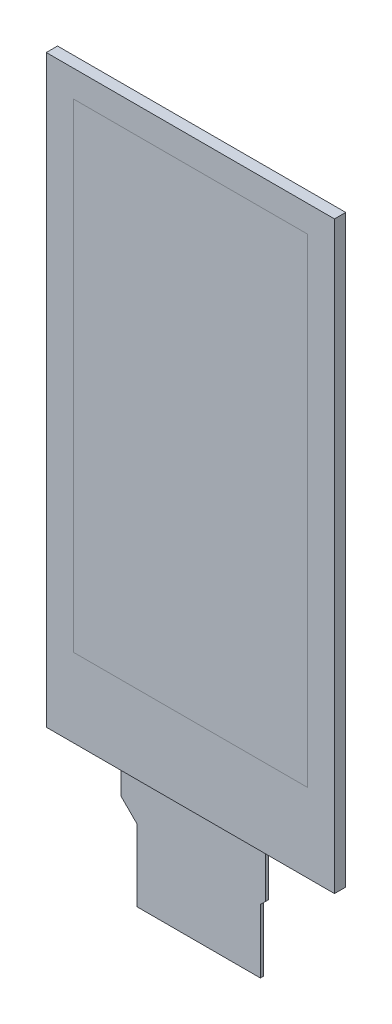
SolidWorks part; units mm, degrees
ref_plane "Front Plane" through (0, 0, 0) normal (0, 0, 1) x (1, 0, 0)
ref_plane "Top Plane" through (0, 0, 0) normal (0, 1, 0) x (1, 0, 0)
ref_plane "Right Plane" through (0, 0, 0) normal (1, 0, 0) x (0, 0, -1)
sketch "Sketch1" plane through (0, 0, 0) normal (0, 0, 1) x (1, 0, 0)
  line L0 (-7.883, -32.225) -> (-7.883, -35.3172)
  line L1 (11.8525, 24.275) -> (-11.8525, 24.275)
  line L2 (11.8525, 24.275) -> (11.8525, -24.275)
  line L3 (11.8525, -24.275) -> (-11.8525, -24.275)
  line L4 (-11.8525, 24.275) -> (-11.8525, -24.275)
  line L5 (0, -24.275) -> (0, 24.275) construction
  line L6 (11.8525, 0) -> (-11.8525, 0) construction
  line L7 (14.6005, 26.975) -> (-14.5995, 26.975)
  line L8 (14.6005, 26.975) -> (14.6005, -32.225)
  line L9 (14.6005, -32.225) -> (-14.5995, -32.225)
  line L10 (-14.5995, 26.975) -> (-14.5995, -32.225)
  line L11 (0.0005, -32.225) -> (0.0005, 26.975) construction
  line L12 (14.6005, -2.625) -> (-14.5995, -2.625) construction
  line L13 (-7.883, -35.3172) -> (-6.2495, -36.9508)
  line L14 (-6.2495, -36.9508) -> (-6.2495, -44.225)
  line L15 (-6.2495, -44.225) -> (6.2505, -44.225)
  line L16 (6.2505, -44.225) -> (6.2505, -37.7718)
  line L17 (6.2505, -37.7718) -> (6.7703, -37.252)
  line L18 (6.7703, -37.252) -> (6.7703, -32.225)
  point P0 (0, 0)
  point P4 (0.0005, -2.625)
  point P10 (0, 0)
  point P17 (15.5111, 26.7095)
  point P18 (6.2505, -35.7718)
  dimension "D1" = 23.705
  dimension "D2" = 29.2
  dimension "D3" = 48.55
  dimension "D4" = 59.2
  dimension "D5" = 12.5
  dimension "D6" = 8.35
  dimension "D7" = 2.748
  dimension "D8" = 2.7
  dimension "D9" = 135
  dimension "D10" = 135
  dimension "D11" = 12
extrude "Boss-Extrude1" add sketch "Sketch1" along normal blind 1.14 contours L1 L4 L3 L2 region at (0, 0, 0)
extrude "Boss-Extrude2" add sketch "Sketch1<3>" along normal blind 1.14 separate body contours L7 L10 L9 L8 L4 L1 L2 L3 region at (-11.2413, -31.5649, 0)
sketch "Sketch1<3>" plane through (0, 0, 0) normal (0, 0, 1) x (1, 0, 0) same geometry as "Sketch1"
extrude "Boss-Extrude3" add sketch "Sketch1<4>" along normal blind 0.3 separate body contours L17 L18 L9 L0 L13 L14 L15 L16 region at (-0.1684, -38.0059, 0)
sketch "Sketch1<4>" plane through (0, 0, 0) normal (0, 0, 1) x (1, 0, 0) same geometry as "Sketch1"
